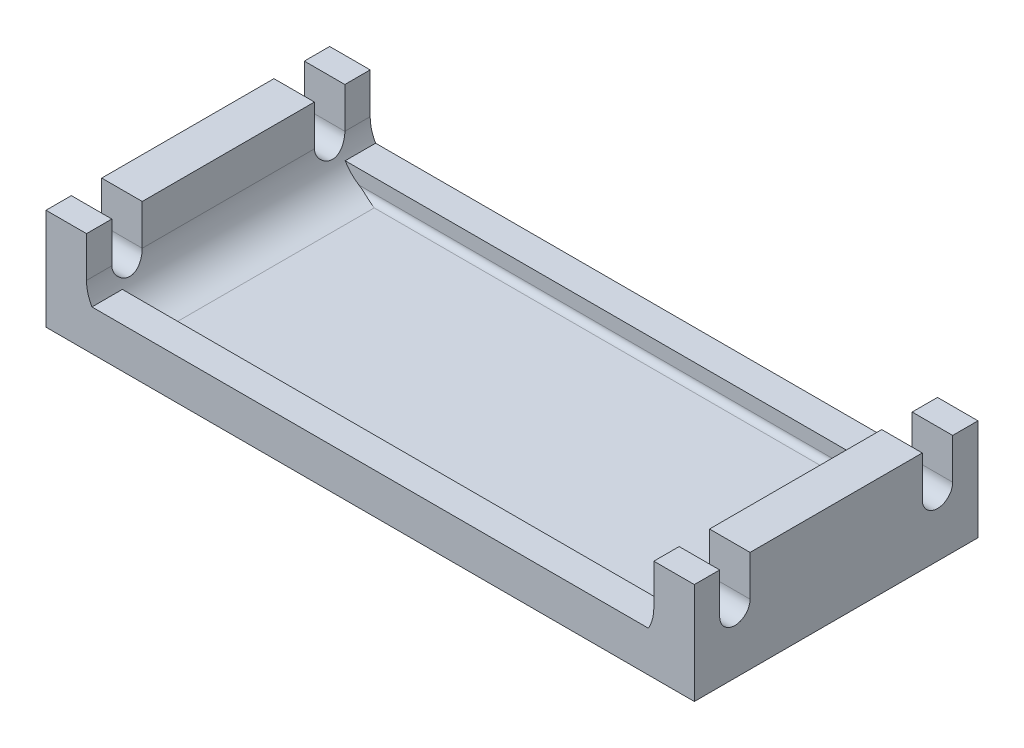
SolidWorks part; units mm, degrees
ref_plane "Front Plane" through (0, 0, 0) normal (0, 0, 1) x (1, 0, 0)
ref_plane "Top Plane" through (0, 0, 0) normal (0, 1, 0) x (1, 0, 0)
ref_plane "Right Plane" through (0, 0, 0) normal (1, 0, 0) x (0, 0, -1)
sketch "Sketch1" plane through (0, 0, 0) normal (0, 1, 0) x (1, 0, 0)
  line L1 (50.8, -22.225) -> (-50.8, -22.225)
  line L2 (50.8, -22.225) -> (50.8, 22.225)
  line L3 (50.8, 22.225) -> (-50.8, 22.225)
  line L4 (-50.8, -22.225) -> (-50.8, 22.225)
  line L5 (50.8, -22.225) -> (-50.8, 22.225) construction
  line L6 (50.8, 22.225) -> (-50.8, -22.225) construction
  point P0 (0, 0)
  dimension "D1" = 101.6
  dimension "D2" = 44.45
extrude "Boss-Extrude1" add sketch "Sketch1" along normal blind 3.175
sketch "Sketch2" plane through (0, 3.175, 0) normal (0, 1, 0) x (1, 0, 0)
  line L0 (-50.8, -22.225) -> (50.8, -22.225) construction
  line L1 (-50.8, 22.225) -> (-44.45, 22.225)
  line L2 (-50.8, 22.225) -> (-50.8, -22.225)
  line L3 (-50.8, -22.225) -> (-44.45, -22.225)
  line L4 (-44.45, 22.225) -> (-44.45, -22.225)
  line L6 (50.8, 22.225) -> (44.45, 22.225)
  line L7 (50.8, 22.225) -> (50.8, -22.225)
  line L8 (50.8, -22.225) -> (44.45, -22.225)
  line L9 (44.45, 22.225) -> (44.45, -22.225)
  dimension "D1" = 6.35
  dimension "D2" = 6.35
extrude "Boss-Extrude2" add sketch "Sketch2" along normal blind 12.7
sketch "Sketch3" plane through (0, 3.175, 0) normal (0, 1, 0) x (1, 0, 0)
  line L0 (-44.45, -22.225) -> (-44.45, 22.225) construction
  line L1 (44.45, -17.4625) -> (-44.45, -17.4625)
  line L2 (44.45, -17.4625) -> (44.45, 17.4625)
  line L3 (44.45, 17.4625) -> (-44.45, 17.4625)
  line L4 (-44.45, -17.4625) -> (-44.45, 17.4625)
  line L5 (44.45, -17.4625) -> (-44.45, 17.4625) construction
  line L6 (44.45, 17.4625) -> (-44.45, -17.4625) construction
  line L7 (44.45, 22.225) -> (-44.45, 22.225) construction
  line L9 (44.45, -22.225) -> (-44.45, -22.225)
  line L10 (44.45, -22.225) -> (44.45, 22.225)
  line L11 (44.45, 22.225) -> (-44.45, 22.225)
  line L12 (-44.45, -22.225) -> (-44.45, 22.225)
  line L13 (44.45, -22.225) -> (-44.45, 22.225) construction
  line L14 (44.45, 22.225) -> (-44.45, -22.225) construction
  point P0 (0, 0)
  point P10 (0, 0)
  line M2 (-44.45, -22.225) -> (44.45, -22.225)
  line M3 (44.45, -22.225) -> (44.45, 22.225)
  line M4 (44.45, 22.225) -> (-44.45, 22.225)
  line M5 (-44.45, 22.225) -> (-44.45, -22.225)
  dimension "D1" = 4.7625
extrude "Boss-Extrude3" add sketch "Sketch3" along normal blind 3.175 contours L3 M3 M4 M5 | L1 M3 M5 M2
fillet "Fillet1" radius 0.9525 2 edges at (0, 3.175, 17.4625) (0, 3.175, -17.4625)
fillet "Fillet2" radius 6.35 2 edges at (44.45, 3.175, 0)
sketch "Sketch4" plane through (50.8, 0, 0) normal (1, 0, 0) x (0, 0, -1)
  line L1 (-22.225, 0) -> (22.225, 0) construction
  line L2 (-22.225, 15.875) -> (-22.225, 0) construction
  line L3 (22.225, 15.875) -> (22.225, 0) construction
  line L4 (-18.2562, 9.525) -> (-18.2562, 15.875)
  line L5 (-22.225, 15.875) -> (22.225, 15.875) construction
  line L6 (-18.2562, 15.875) -> (-13.4937, 15.875)
  line L7 (-13.4937, 15.875) -> (-13.4937, 9.525)
  line L8 (13.4938, 9.525) -> (13.4938, 15.875)
  line L9 (13.4938, 15.875) -> (18.2563, 15.875)
  line L10 (18.2563, 15.875) -> (18.2563, 9.525)
  circle A0 centre (-15.875, 9.525) radius 2.3813
  circle A1 centre (15.875, 9.525) radius 2.3813
  line M3 (22.225, 15.875) -> (-22.225, 15.875)
  dimension "D2" = 6.35
  dimension "D4" = 4.7625
  dimension "D5" = 4.7625
  dimension "D1" = 9.525
  dimension "D3" = 6.35
extrude "Cut-Extrude1" cut sketch "Sketch4" against normal through all contours A0 L7 L4 M3 | A0 | A1 | A1 L10 L8 M3
